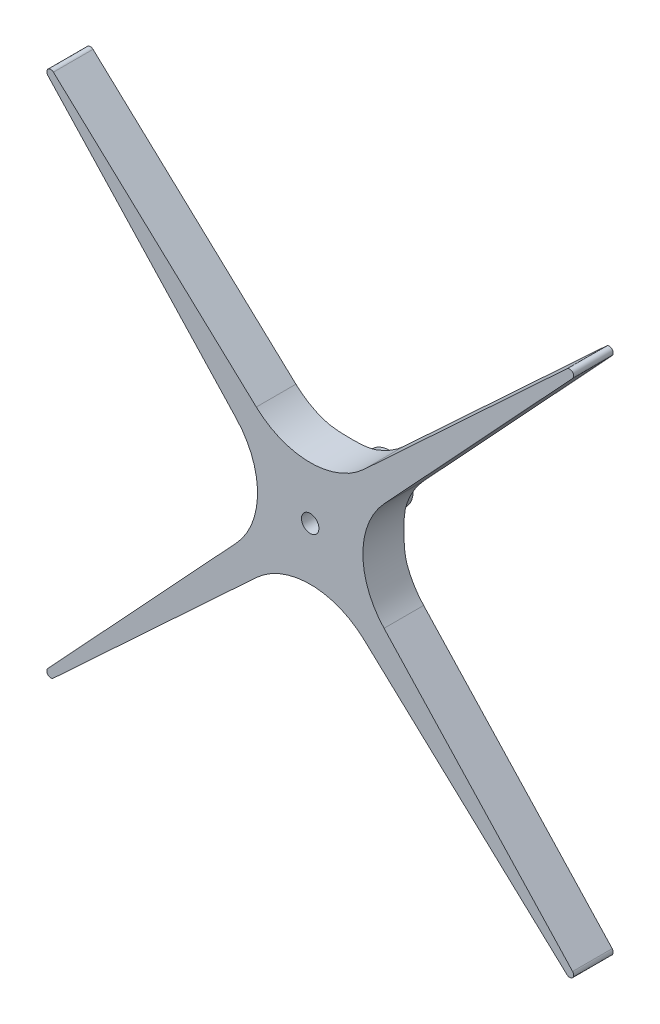
SolidWorks part; units mm, degrees
ref_plane "前视基准面" through (0, 0, 0) normal (0, 0, 1) x (1, 0, 0)
ref_plane "上视基准面" through (0, 0, 0) normal (0, 1, 0) x (1, 0, 0)
ref_plane "右视基准面" through (0, 0, 0) normal (1, 0, 0) x (0, 0, -1)
sketch "草图1" plane through (0, 0, 0) normal (0, 0, 1) x (1, 0, 0)
  circle A0 centre (0, 0) radius 3
  circle A1 centre (0, 0) radius 1.1
  dimension "D1" = 6
  dimension "D2" = 2.2
extrude "凸台-拉伸1" add sketch "草图1" along normal blind 5
sketch "草图2" plane through (0, 0, 5) normal (0, 0, 1) x (1, 0, 0)
  line L0 (-3, 0) -> (-33.1397, 32.4331)
  line L1 (-32.4331, 33.1397) -> (0, 3)
  line L2 (0, 3) -> (0, 0) construction
  line L3 (0, 0) -> (-3.3406, 3.3406) construction
  line L4 (0, 3) -> (32.4331, 33.1397)
  line L5 (33.1397, 32.4331) -> (3, 0)
  line L6 (3, 0) -> (33.1397, -32.4331)
  line L7 (32.4331, -33.1397) -> (0, -3)
  line L8 (0, -3) -> (-32.4331, -33.1397)
  line L9 (-33.1397, -32.4331) -> (-3, 0)
  circle A0 centre (0, 0) radius 3 construction
  arc A1 (-33.1397, 32.4331) -> (-32.4331, 33.1397) centre (-32.7735, 32.7735) cw
  arc A2 (32.4331, 33.1397) -> (33.1397, 32.4331) centre (32.7735, 32.7735) cw
  circle A3 centre (0, 0) radius 3
  circle A4 centre (0, 0) radius 3
  arc A5 (33.1397, -32.4331) -> (32.4331, -33.1397) centre (32.7735, -32.7735) cw
  arc A6 (-32.4331, -33.1397) -> (-33.1397, -32.4331) centre (-32.7735, -32.7735) cw
  point P11 (-42.4264, 42.4264)
  circle M6 centre (0, 0) radius 3
  dimension "D3" = 0.5
  dimension "D1" = 45
  dimension "D2" = 60
  dimension "D4" = 0
  dimension "D5" = 4
extrude "凸台-拉伸2" add sketch "草图2" along normal blind 5 contours A1 L0 L1 M6 | A2 L4 L5 M6 | A5 L6 L7 M6 | A6 L8 L9 M6 region at (-14.2542, -14.2542, 5) region at (-14.2542, 14.2542, 5) region at (14.2542, 14.2542, 5) region at (14.2542, -14.2542, 5)
sketch "草图3" plane through (0, 0, 10) normal (0, 0, 1) x (1, 0, 0)
  circle A0 centre (0, 0) radius 1.1 construction
  circle A1 centre (0, 0) radius 3
  circle A2 centre (0, 0) radius 3
  circle A3 centre (0, 0) radius 1.1
  dimension "D1" = 0
extrude "凸台-拉伸3" add sketch "草图3" against normal blind 5
fillet "圆角1" radius 5 4 edges at (-2.1213, -2.1213, 5) (-2.1213, 2.1213, 5) (2.1213, 2.1213, 5) (2.1213, -2.1213, 5)
fillet "圆角2" radius 10 4 edges at (3, 0, 5) (0, 3, 5) (-3, 0, 5) (0, -3, 5)
